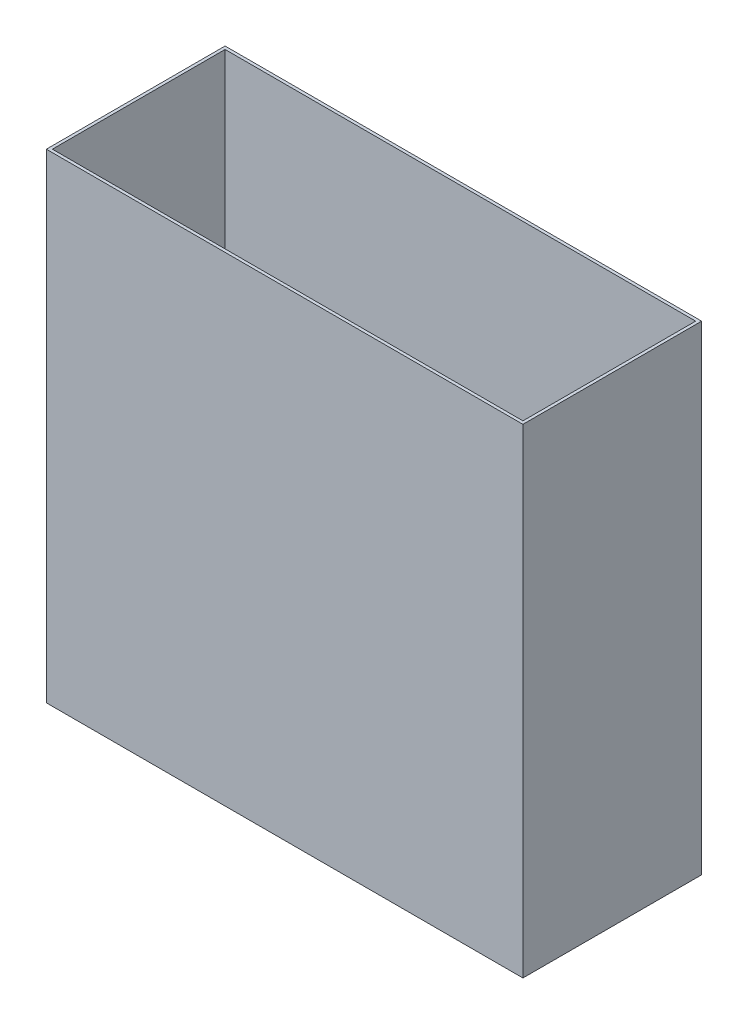
SolidWorks part; units mm, degrees
ref_plane "Front Plane" through (0, 0, 0) normal (0, 0, 1) x (1, 0, 0)
ref_plane "Top Plane" through (0, 0, 0) normal (0, 1, 0) x (1, 0, 0)
ref_plane "Right Plane" through (0, 0, 0) normal (1, 0, 0) x (0, 0, -1)
sketch "Sketch1" plane through (0, 0, 0) normal (0, 1, 0) x (1, 0, 0)
  line L0 (-200.66, 73.66) -> (200.66, 73.66)
  line L1 (-203.2, 76.2) -> (203.2, 76.2)
  line L2 (-203.2, 76.2) -> (-203.2, -76.2)
  line L3 (-203.2, -76.2) -> (203.2, -76.2)
  line L4 (203.2, 76.2) -> (203.2, -76.2)
  line L5 (-203.2, 76.2) -> (203.2, -76.2) construction
  line L6 (-203.2, -76.2) -> (203.2, 76.2) construction
  line L7 (200.66, 73.66) -> (200.66, -73.66)
  line L8 (-200.66, -73.66) -> (200.66, -73.66)
  line L9 (-200.66, 73.66) -> (-200.66, -73.66)
  point P4 (0, 0)
  dimension "D1" = 406.4
  dimension "D2" = 152.4
  dimension "D3" = 2.54
extrude "Boss-Extrude1" add sketch "Sketch1" along normal blind 406.4
sketch "Sketch2" plane through (0, 0, 0) normal (0, -1, 0) x (1, 0, 0)
  line L0 (203.2, 76.2) -> (203.2, -76.2) construction
  line L1 (-203.2, -76.2) -> (-203.2, 76.2) construction
  line L2 (-203.2, 76.2) -> (203.2, 76.2) construction
  line L3 (203.2, -76.2) -> (-203.2, -76.2) construction
  line L4 (203.2, 76.2) -> (203.2, -76.2)
  line L5 (-203.2, -76.2) -> (-203.2, 76.2)
  line L6 (-203.2, 76.2) -> (203.2, 76.2)
  line L7 (203.2, -76.2) -> (-203.2, -76.2)
extrude "Boss-Extrude2" add sketch "Sketch2" along normal blind 2.54
